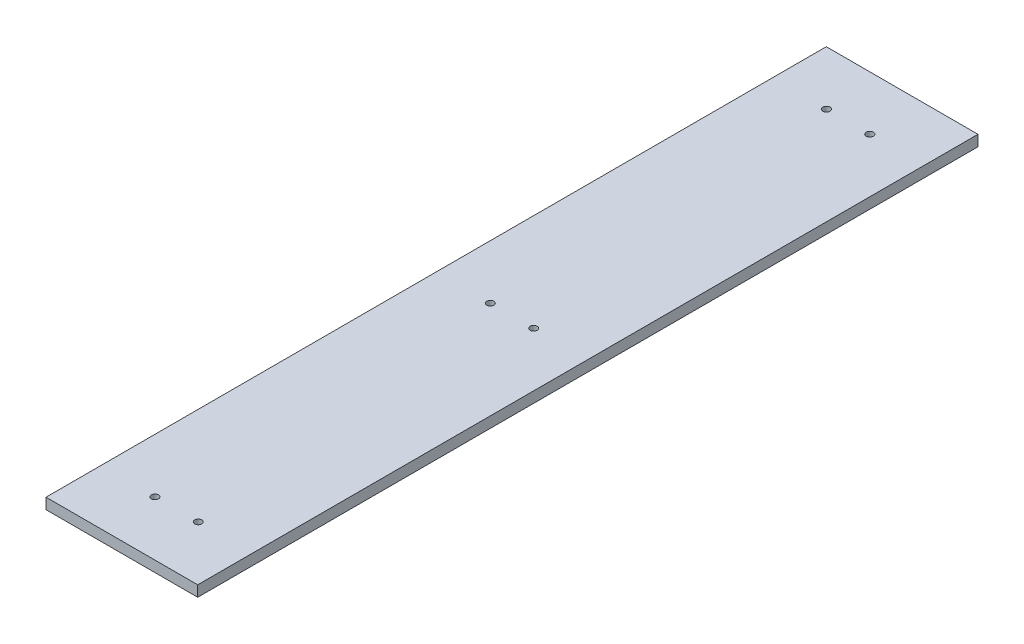
SolidWorks part; units mm, degrees
material "Pine"
ref_plane "Front Plane" through (0, 0, 0) normal (0, 0, 1) x (1, 0, 0)
ref_plane "Top Plane" through (0, 0, 0) normal (0, 1, 0) x (1, 0, 0)
ref_plane "Right Plane" through (0, 0, 0) normal (1, 0, 0) x (0, 0, -1)
sketch "Sketch1" plane through (0, 0, 0) normal (0, 0, 1) x (1, 0, 0)
  line L0 (-44.45, 38.1) -> (-44.45, 6.35) construction
  line L1 (44.45, -38.1) -> (-44.45, -38.1)
  line L2 (44.45, -38.1) -> (44.45, -44.45)
  line L3 (44.45, -44.45) -> (-44.45, -44.45)
  line L4 (-44.45, -38.1) -> (-44.45, -44.45)
  dimension "D1" = 6.35
extrude "Boss-Extrude1" add sketch "Sketch1" against normal up to surface (457.2 mm away)
sketch "Sketch2" plane through (0, -44.45, 0) normal (0, -1, 0) x (1, 0, 0)
  circle A0 centre (-12.7, -228.6) radius 2.0638
  circle A1 centre (-12.7, -228.6) radius 2.0638 construction
  circle A2 centre (12.7, -228.6) radius 2.0638
  circle A3 centre (12.7, -228.6) radius 2.0638 construction
  circle A4 centre (-12.7, -32.0675) radius 2.0638
  circle A5 centre (-12.7, -32.0675) radius 2.0638 construction
  circle A6 centre (12.7, -32.0675) radius 2.0638
  circle A7 centre (12.7, -32.0675) radius 2.0638 construction
extrude "Cut-Extrude1" cut sketch "Sketch2" against normal through all
sketch "Sketch3" plane through (0, -44.45, 0) normal (0, -1, 0) x (-1, 0, 0)
  circle A0 centre (12.7, 425.5516) radius 2.0955
  circle A1 centre (-12.7, 425.5516) radius 2.0955
  circle A2 centre (-12.7, 425.5516) radius 2.0955 construction
  circle A3 centre (12.7, 425.5516) radius 2.0955 construction
extrude "Cut-Extrude2" cut sketch "Sketch3" against normal through all
